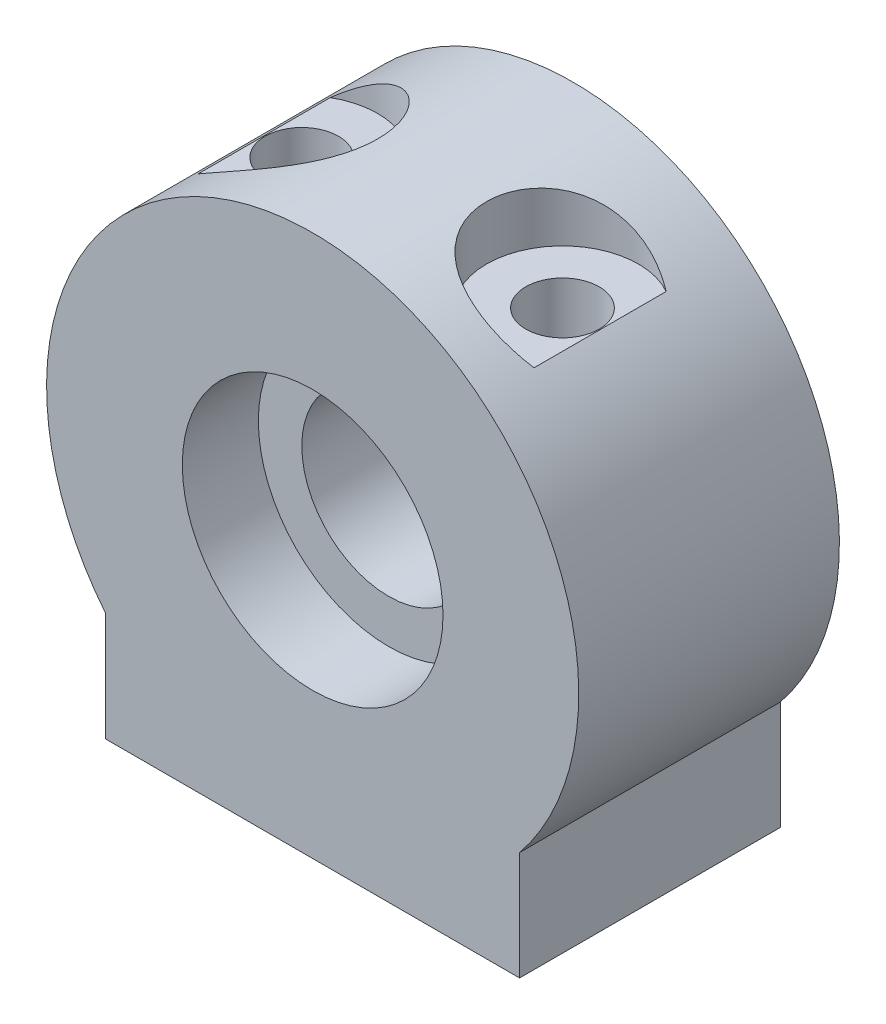
SolidWorks part; units mm, degrees
ref_plane "Front Plane" through (0, 0, 0) normal (0, 0, 1) x (1, 0, 0)
ref_plane "Top Plane" through (0, 0, 0) normal (0, 1, 0) x (1, 0, 0)
ref_plane "Right Plane" through (0, 0, 0) normal (1, 0, 0) x (0, 0, -1)
sketch "Sketch1" plane through (0, 0, 0) normal (0, 0, 1) x (1, 0, 0)
  line L0 (-19.05, -25.4) -> (19.05, -25.4)
  line L1 (19.05, -25.4) -> (19.05, -15.4)
  line L3 (-19.05, -25.4) -> (-19.05, -15.4)
  line L5 (0, -36.0367) -> (0, 36.0367) construction
  circle A0 centre (0, 0) radius 12
  arc A1 (-19.05, -15.4) -> (19.05, -15.4) centre (0, 0) cw
  point P9 (0, -25.4)
  dimension "D1" = 24
  dimension "D2" = 38.1
  dimension "D3" = 10
  dimension "D4" = 25.4
extrude "Boss-Extrude1" add sketch "Sketch1" along normal blind 7
sketch "Sketch2" plane through (0, 0, 0) normal (0, 0, 1) x (1, 0, 0)
  line L0 (-19.05, -25.4) -> (19.05, -25.4)
  line L1 (19.05, -25.4) -> (19.05, -15.4)
  line L3 (-19.05, -25.4) -> (-19.05, -15.4)
  circle A0 centre (0, 0) radius 8
  arc A1 (-19.05, -15.4) -> (19.05, -15.4) centre (0, 0) cw
  dimension "D1" = 16
  dimension "D2" = 38.1
  dimension "D3" = 10
  dimension "D4" = 25.4
extrude "Boss-Extrude2" add sketch "Sketch2" against normal blind 17
sketch "Sketch3" plane through (0, 0, 0) normal (0, 1, 0) x (1, 0, 0)
  line L0 (-12, 4) -> (12, 4) construction
  line L1 (0, -13.2) -> (0, 13.2) construction
  circle A0 centre (-12, 4) radius 3.38
  circle A1 centre (12, 4) radius 3.38
  point P4 (0, 4)
  dimension "D1" = 24
  dimension "D2" = 6.76
  dimension "D3" = 6.76
  dimension "D4" = 4
extrude "Cut-Extrude1" cut sketch "Sketch3" against normal through all both and the other way through all
sketch "Sketch4" plane through (0, 0, 0) normal (0, 1, 0) x (1, 0, 0)
  circle A0 centre (-12, 4) radius 7
  circle A1 centre (12, 4) radius 7
  dimension "D1" = 14
extrude "Cut-Extrude2" cut sketch "Sketch4" against normal blind 17 from offset 36
equation "\"bearingOuterDiameter\"= 24mm"
equation "\"bearingDepth\"= 7mm"
equation "\"holeDiameter\"= 6.76mm"
equation "\"D1@Sketch1\"=\"bearingOuterDiameter\""
equation "\"D2@Sketch1\"=25.4*1.5"
equation "\"D1@Boss-Extrude1\"=\"bearingDepth\""
equation "\"D2@Sketch3\"=\"holeDiameter\""
equation "\"D3@Sketch3\"=\"holeDiameter\""
